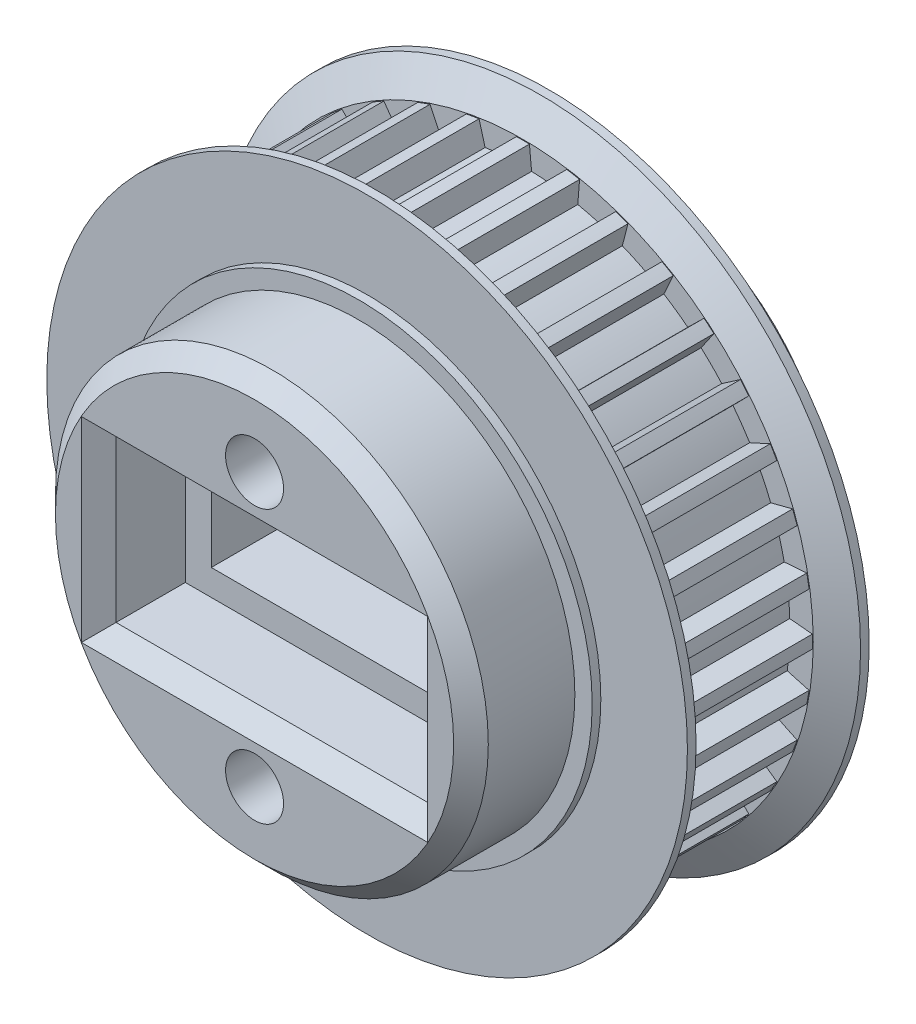
SolidWorks part; units mm, degrees
material "ABS"
ref_plane "Alzado" through (0, 0, 0) normal (0, 0, 1) x (1, 0, 0)
ref_plane "Planta" through (0, 0, 0) normal (0, 1, 0) x (1, 0, 0)
ref_plane "Vista lateral" through (0, 0, 0) normal (1, 0, 0) x (0, 0, -1)
sketch "Croquis1" plane through (0, 0, 0) normal (0, 0, 1) x (1, 0, 0)
  line L0 (0, 0) -> (0, 14.5885) construction
  line L1 (-0.375, 16.7142) -> (-0.5, 15.4103)
  line L2 (0.375, 16.7142) -> (0.5, 15.4103)
  line L3 (3.2717, 16.3952) -> (3.1684, 15.0894)
  line L4 (2.5331, 16.5254) -> (2.1836, 15.263)
  line L5 (6.069, 15.578) -> (5.7405, 14.3099)
  line L6 (5.3642, 15.8345) -> (4.8008, 14.652)
  line L7 (8.6819, 14.2874) -> (8.1382, 13.0957)
  line L8 (8.0323, 14.6624) -> (7.2721, 13.5957)
  line L9 (11.031, 12.5628) -> (10.2886, 11.4836)
  line L10 (10.4564, 13.0449) -> (9.5225, 12.1264)
  line L11 (13.0449, 10.4564) -> (12.1264, 9.5225)
  line L12 (12.5628, 11.031) -> (11.4836, 10.2886)
  line L13 (14.6624, 8.0323) -> (13.5957, 7.2721)
  line L14 (14.2874, 8.6819) -> (13.0957, 8.1382)
  line L15 (15.8345, 5.3642) -> (14.652, 4.8008)
  line L16 (15.578, 6.069) -> (14.3099, 5.7405)
  line L17 (16.5254, 2.5331) -> (15.263, 2.1836)
  line L18 (16.3952, 3.2717) -> (15.0894, 3.1684)
  line L19 (16.7142, -0.375) -> (15.4103, -0.5)
  line L20 (16.7142, 0.375) -> (15.4103, 0.5)
  line L21 (16.3952, -3.2717) -> (15.0894, -3.1684)
  line L22 (16.5254, -2.5331) -> (15.263, -2.1836)
  line L23 (15.578, -6.069) -> (14.3099, -5.7405)
  line L24 (15.8345, -5.3642) -> (14.652, -4.8008)
  line L25 (14.2874, -8.6819) -> (13.0957, -8.1382)
  line L26 (14.6624, -8.0323) -> (13.5957, -7.2721)
  line L27 (12.5628, -11.031) -> (11.4836, -10.2886)
  line L28 (13.0449, -10.4564) -> (12.1264, -9.5225)
  line L29 (10.4564, -13.0449) -> (9.5225, -12.1264)
  line L30 (11.031, -12.5628) -> (10.2886, -11.4836)
  line L31 (8.0323, -14.6624) -> (7.2721, -13.5957)
  line L32 (8.6819, -14.2874) -> (8.1382, -13.0957)
  line L33 (5.3642, -15.8345) -> (4.8008, -14.652)
  line L34 (6.069, -15.578) -> (5.7405, -14.3099)
  line L35 (2.5331, -16.5254) -> (2.1836, -15.263)
  line L36 (3.2717, -16.3952) -> (3.1684, -15.0894)
  line L37 (-0.375, -16.7142) -> (-0.5, -15.4103)
  line L38 (0.375, -16.7142) -> (0.5, -15.4103)
  line L39 (-3.2717, -16.3952) -> (-3.1684, -15.0894)
  line L40 (-2.5331, -16.5254) -> (-2.1836, -15.263)
  line L41 (-6.069, -15.578) -> (-5.7405, -14.3099)
  line L42 (-5.3642, -15.8345) -> (-4.8008, -14.652)
  line L43 (-8.6819, -14.2874) -> (-8.1382, -13.0957)
  line L44 (-8.0323, -14.6624) -> (-7.2721, -13.5957)
  line L45 (-11.031, -12.5628) -> (-10.2886, -11.4836)
  line L46 (-10.4564, -13.0449) -> (-9.5225, -12.1264)
  line L47 (-13.0449, -10.4564) -> (-12.1264, -9.5225)
  line L48 (-12.5628, -11.031) -> (-11.4836, -10.2886)
  line L49 (-14.6624, -8.0323) -> (-13.5957, -7.2721)
  line L50 (-14.2874, -8.6819) -> (-13.0957, -8.1382)
  line L51 (-15.8345, -5.3642) -> (-14.652, -4.8008)
  line L52 (-15.578, -6.069) -> (-14.3099, -5.7405)
  line L53 (-16.5254, -2.5331) -> (-15.263, -2.1836)
  line L54 (-16.3952, -3.2717) -> (-15.0894, -3.1684)
  line L55 (-16.7142, 0.375) -> (-15.4103, 0.5)
  line L56 (-16.7142, -0.375) -> (-15.4103, -0.5)
  line L57 (-16.3952, 3.2717) -> (-15.0894, 3.1684)
  line L58 (-16.5254, 2.5331) -> (-15.263, 2.1836)
  line L59 (-15.578, 6.069) -> (-14.3099, 5.7405)
  line L60 (-15.8345, 5.3642) -> (-14.652, 4.8008)
  line L61 (-14.2874, 8.6819) -> (-13.0957, 8.1382)
  line L62 (-14.6624, 8.0323) -> (-13.5957, 7.2721)
  line L63 (-12.5628, 11.031) -> (-11.4836, 10.2886)
  line L64 (-13.0449, 10.4564) -> (-12.1264, 9.5225)
  line L65 (-10.4564, 13.0449) -> (-9.5225, 12.1264)
  line L66 (-11.031, 12.5628) -> (-10.2886, 11.4836)
  line L67 (-8.0323, 14.6624) -> (-7.2721, 13.5957)
  line L68 (-8.6819, 14.2874) -> (-8.1382, 13.0957)
  line L69 (-5.3642, 15.8345) -> (-4.8008, 14.652)
  line L70 (-6.069, 15.578) -> (-5.7405, 14.3099)
  line L71 (-2.5331, 16.5254) -> (-2.1836, 15.263)
  line L72 (-3.2717, 16.3952) -> (-3.1684, 15.0894)
  arc A0 (-10.4564, 13.0449) -> (-11.031, 12.5628) centre (0, 0) ccw
  arc A1 (2.1836, 15.263) -> (0.5, 15.4103) centre (0, 0) ccw
  arc A2 (-12.5628, 11.031) -> (-13.0449, 10.4564) centre (0, 0) ccw
  arc A3 (-14.2874, 8.6819) -> (-14.6624, 8.0323) centre (0, 0) ccw
  arc A4 (-15.578, 6.069) -> (-15.8345, 5.3642) centre (0, 0) ccw
  arc A5 (-16.3952, 3.2717) -> (-16.5254, 2.5331) centre (0, 0) ccw
  arc A6 (-16.7142, 0.375) -> (-16.7142, -0.375) centre (0, 0) ccw
  arc A7 (-16.5254, -2.5331) -> (-16.3952, -3.2717) centre (0, 0) ccw
  arc A8 (-15.8345, -5.3642) -> (-15.578, -6.069) centre (0, 0) ccw
  arc A9 (-14.6624, -8.0323) -> (-14.2874, -8.6819) centre (0, 0) ccw
  arc A10 (-13.0449, -10.4564) -> (-12.5628, -11.031) centre (0, 0) ccw
  arc A11 (3.2717, 16.3952) -> (2.5331, 16.5254) centre (0, 0) ccw
  arc A12 (0.375, 16.7142) -> (-0.375, 16.7142) centre (0, 0) ccw
  arc A13 (-5.3642, 15.8345) -> (-6.069, 15.578) centre (0, 0) ccw
  arc A14 (-8.0323, 14.6624) -> (-8.6819, 14.2874) centre (0, 0) ccw
  arc A15 (-2.5331, 16.5254) -> (-3.2717, 16.3952) centre (0, 0) ccw
  arc A16 (6.069, 15.578) -> (5.3642, 15.8345) centre (0, 0) ccw
  arc A17 (8.6819, 14.2874) -> (8.0323, 14.6624) centre (0, 0) ccw
  arc A18 (11.031, 12.5628) -> (10.4564, 13.0449) centre (0, 0) ccw
  arc A19 (13.0449, 10.4564) -> (12.5628, 11.031) centre (0, 0) ccw
  arc A20 (14.6624, 8.0323) -> (14.2874, 8.6819) centre (0, 0) ccw
  arc A21 (15.8345, 5.3642) -> (15.578, 6.069) centre (0, 0) ccw
  arc A22 (16.5254, 2.5331) -> (16.3952, 3.2717) centre (0, 0) ccw
  arc A23 (16.7142, -0.375) -> (16.7142, 0.375) centre (0, 0) ccw
  arc A24 (16.3952, -3.2717) -> (16.5254, -2.5331) centre (0, 0) ccw
  arc A25 (15.578, -6.069) -> (15.8345, -5.3642) centre (0, 0) ccw
  arc A26 (8.0323, -14.6624) -> (8.6819, -14.2874) centre (0, 0) ccw
  arc A27 (5.3642, -15.8345) -> (6.069, -15.578) centre (0, 0) ccw
  arc A28 (2.5331, -16.5254) -> (3.2717, -16.3952) centre (0, 0) ccw
  arc A29 (-3.2717, -16.3952) -> (-2.5331, -16.5254) centre (0, 0) ccw
  arc A30 (-6.069, -15.578) -> (-5.3642, -15.8345) centre (0, 0) ccw
  arc A31 (-8.6819, -14.2874) -> (-8.0323, -14.6624) centre (0, 0) ccw
  arc A32 (-11.031, -12.5628) -> (-10.4564, -13.0449) centre (0, 0) ccw
  arc A33 (10.4564, -13.0449) -> (11.031, -12.5628) centre (0, 0) ccw
  arc A34 (12.5628, -11.031) -> (13.0449, -10.4564) centre (0, 0) ccw
  arc A35 (14.2874, -8.6819) -> (14.6624, -8.0323) centre (0, 0) ccw
  arc A36 (4.8008, 14.652) -> (3.1684, 15.0894) centre (0, 0) ccw
  arc A37 (7.2721, 13.5957) -> (5.7405, 14.3099) centre (0, 0) ccw
  arc A38 (-3.1684, 15.0894) -> (-4.8008, 14.652) centre (0, 0) ccw
  arc A39 (-0.5, 15.4103) -> (-2.1836, 15.263) centre (0, 0) ccw
  arc A40 (-5.7405, 14.3099) -> (-7.2721, 13.5957) centre (0, 0) ccw
  arc A41 (-8.1382, 13.0957) -> (-9.5225, 12.1264) centre (0, 0) ccw
  arc A42 (-10.2886, 11.4836) -> (-11.4836, 10.2886) centre (0, 0) ccw
  arc A43 (9.5225, 12.1264) -> (8.1382, 13.0957) centre (0, 0) ccw
  arc A44 (11.4836, 10.2886) -> (10.2886, 11.4836) centre (0, 0) ccw
  arc A45 (13.0957, 8.1382) -> (12.1264, 9.5225) centre (0, 0) ccw
  arc A46 (14.3099, 5.7405) -> (13.5957, 7.2721) centre (0, 0) ccw
  arc A47 (15.0894, 3.1684) -> (14.652, 4.8008) centre (0, 0) ccw
  arc A48 (15.4103, 0.5) -> (15.263, 2.1836) centre (0, 0) ccw
  arc A49 (15.263, -2.1836) -> (15.4103, -0.5) centre (0, 0) ccw
  arc A50 (14.652, -4.8008) -> (15.0894, -3.1684) centre (0, 0) ccw
  arc A51 (13.5957, -7.2721) -> (14.3099, -5.7405) centre (0, 0) ccw
  arc A52 (12.1264, -9.5225) -> (13.0957, -8.1382) centre (0, 0) ccw
  arc A53 (10.2886, -11.4836) -> (11.4836, -10.2886) centre (0, 0) ccw
  arc A54 (8.1382, -13.0957) -> (9.5225, -12.1264) centre (0, 0) ccw
  arc A55 (5.7405, -14.3099) -> (7.2721, -13.5957) centre (0, 0) ccw
  arc A56 (3.1684, -15.0894) -> (4.8008, -14.652) centre (0, 0) ccw
  arc A57 (0.5, -15.4103) -> (2.1836, -15.263) centre (0, 0) ccw
  arc A58 (-2.1836, -15.263) -> (-0.5, -15.4103) centre (0, 0) ccw
  arc A59 (-4.8008, -14.652) -> (-3.1684, -15.0894) centre (0, 0) ccw
  arc A60 (-7.2721, -13.5957) -> (-5.7405, -14.3099) centre (0, 0) ccw
  arc A61 (-9.5225, -12.1264) -> (-8.1382, -13.0957) centre (0, 0) ccw
  arc A62 (-11.4836, -10.2886) -> (-10.2886, -11.4836) centre (0, 0) ccw
  arc A63 (-13.0957, -8.1382) -> (-12.1264, -9.5225) centre (0, 0) ccw
  arc A64 (-14.3099, -5.7405) -> (-13.5957, -7.2721) centre (0, 0) ccw
  arc A65 (-15.0894, -3.1684) -> (-14.652, -4.8008) centre (0, 0) ccw
  arc A66 (-15.4103, -0.5) -> (-15.263, -2.1836) centre (0, 0) ccw
  arc A67 (-15.263, 2.1836) -> (-15.4103, 0.5) centre (0, 0) ccw
  arc A68 (-14.652, 4.8008) -> (-15.0894, 3.1684) centre (0, 0) ccw
  arc A69 (-13.5957, 7.2721) -> (-14.3099, 5.7405) centre (0, 0) ccw
  arc A70 (-12.1264, 9.5225) -> (-13.0957, 8.1382) centre (0, 0) ccw
  arc A71 (-0.375, -16.7142) -> (0.375, -16.7142) centre (0, 0) ccw
  circle A72 centre (0, 0) radius 2
  point P151 (0, 0)
  dimension "D1" = 1.3
  dimension "D6" = 4
  dimension "D2" = 1
  dimension "D3" = 0.75
  dimension "D5" = 1.69
  dimension "D4" = 36
extrude "Saliente-Extruir1" add sketch "Croquis1" along normal blind 7.5
sketch "Croquis2" plane through (0, 0, 7.5) normal (0, 0, 1) x (1, 0, 0)
  circle A0 centre (0, 0) radius 18.5
  circle A1 centre (0, 0) radius 2
  circle A2 centre (0, 0) radius 2 construction
  dimension "D1" = 37
extrude "Saliente-Extruir2" add sketch "Croquis2" along normal blind 1.5
sketch "Croquis3" plane through (0, 0, 9) normal (0, 0, 1) x (1, 0, 0)
  circle A0 centre (0, 0) radius 2
  circle A1 centre (0, 0) radius 12.5
  circle A3 centre (0, 0) radius 2 construction
  dimension "D1" = 25
sketch "Croquis4" plane through (0, 0, 0) normal (0, 0, -1) x (-1, 0, 0)
  circle A0 centre (0, 0) radius 2
  circle A1 centre (0, 0) radius 12.5
  circle A2 centre (0, 0) radius 2 construction
  dimension "D1" = 25
extrude "Saliente-Extruir4" add sketch "Croquis4" along normal blind 6.5
sketch "Croquis6" plane through (0, 0, 0) normal (0, 0, -1) x (-1, 0, 0)
  circle A0 centre (0, 0) radius 18.5
  circle A1 centre (0, 0) radius 2
  circle A2 centre (0, 0) radius 2 construction
  dimension "D1" = 37
extrude "Saliente-Extruir6" add sketch "Croquis6" along normal blind 1.5
sketch "Croquis5" plane through (0, 0, -1.5) normal (0, 0, -1) x (-1, 0, 0)
  circle A0 centre (0, 0) radius 2
  circle A1 centre (0, 0) radius 13.5
  circle A2 centre (0, 0) radius 2 construction
  dimension "D1" = 27
extrude "Saliente-Extruir5" add sketch "Croquis5" along normal blind 0.5
chamfer "Chaflán2" distance 1 angle 60 2 edges at (-18.5, 0, 0) (18.5, 0, 7.5)
extrude "Saliente-Extruir7" add sketch "Croquis3" along normal blind 6.5
chamfer "Chaflán4" distance 1 angle 45 2 edges at (-12.5, 0, -6.5) (12.5, 0, 15.5)
sketch "Croquis7" plane through (0, 0, 9) normal (0, 0, 1) x (1, 0, 0)
  circle A0 centre (0, 0) radius 2
  circle A1 centre (0, 0) radius 13.5
  circle A2 centre (0, 0) radius 2 construction
  dimension "D1" = 27
extrude "Saliente-Extruir8" add sketch "Croquis7" along normal blind 0.5
sketch "Croquis8" plane through (0, 0, 0) normal (0, 0, 1) x (1, 0, 0)
  line L0 (0, 0) -> (6.706, 0) construction
  line L1 (-7.5, 3.15) -> (7.5, 3.15)
  line L2 (-7.5, 3.15) -> (-7.5, -3.15)
  line L3 (-7.5, -3.15) -> (7.5, -3.15)
  line L4 (7.5, 3.15) -> (7.5, -3.15)
  line L5 (-7.5, 3.15) -> (7.5, -3.15) construction
  line L6 (-7.5, -3.15) -> (7.5, 3.15) construction
  circle A0 centre (0, 7.8756) radius 1.675
  circle A1 centre (0, -7.8756) radius 1.675
  point P0 (0, 0)
  dimension "D1" = 3.35
  dimension "D2" = 6.3
  dimension "D3" = 15
extrude "Cortar-Extruir1" cut sketch "Croquis8" against normal through all both and the other way through all
sketch "Croquis9" plane through (0, 0, -6.5) normal (0, 0, -1) x (-1, 0, 0)
  line L1 (2.3383, 3.8256) -> (4.6765, 7.8756)
  line L2 (4.6765, 7.8756) -> (2.3383, 11.9256)
  line L3 (2.3383, 11.9256) -> (-2.3383, 11.9256)
  line L4 (-2.3383, 11.9256) -> (-4.6765, 7.8756)
  line L5 (-4.6765, 7.8756) -> (-2.3383, 3.8256)
  line L6 (-2.3383, 3.8256) -> (2.3383, 3.8256)
  line L7 (2.3383, -11.9256) -> (4.6765, -7.8756)
  line L8 (4.6765, -7.8756) -> (2.3383, -3.8256)
  line L9 (2.3383, -3.8256) -> (-2.3383, -3.8256)
  line L10 (-2.3383, -3.8256) -> (-4.6765, -7.8756)
  line L11 (-4.6765, -7.8756) -> (-2.3383, -11.9256)
  line L12 (-2.3383, -11.9256) -> (2.3383, -11.9256)
  circle A0 centre (0, 7.8756) radius 4.05 construction
  circle A1 centre (0, -7.8756) radius 4.05 construction
  dimension "D1" = 8.1
extrude "Cortar-Extruir2" cut sketch "Croquis9" against normal blind 7
fillet "Redondeo1" radius 2.5 12 edges at (3.5074, -9.9006, 0.5) (3.5074, -5.8506, 0.5) (0, -3.8256, 0.5) (-3.5074, -5.8506, 0.5) (0, -11.9256, 0.5) (-3.5074, -9.9006, 0.5) (-3.5074, 5.8506, 0.5) (-3.5074, 9.9006, 0.5) (0, 11.9256, 0.5) (3.5074, 9.9006, 0.5) (3.5074, 5.8506, 0.5) (0, 3.8256, 0.5)
sketch "Croquis10" plane through (0, 0, 15.5) normal (0, 0, 1) x (1, 0, 0)
  line L0 (7.5, 3.15) -> (-7.5, 3.15) construction
  line L1 (9, 4.65) -> (-9, 4.65)
  line L2 (9, 4.65) -> (9, -4.65)
  line L3 (9, -4.65) -> (-9, -4.65)
  line L4 (-9, 4.65) -> (-9, -4.65)
  line L5 (9, 4.65) -> (-9, -4.65) construction
  line L6 (9, -4.65) -> (-9, 4.65) construction
  line L7 (-7.5, 3.15) -> (-7.5, -3.15) construction
  point P0 (0, 0)
  dimension "D1" = 1.5
  dimension "D2" = 1.5
extrude "Cortar-Extruir3" cut sketch "Croquis10" against normal blind 5
chamfer "Chaflán5" distance 1 angle 45 8 edges at (-7.5, 0, -6.5) (0, 3.15, -6.5) (7.5, 0, -6.5) (0, -3.15, -6.5) (9, 0, 15.5) (0, 4.65, 15.5) (-9, 0, 15.5) (0, -4.65, 15.5)
